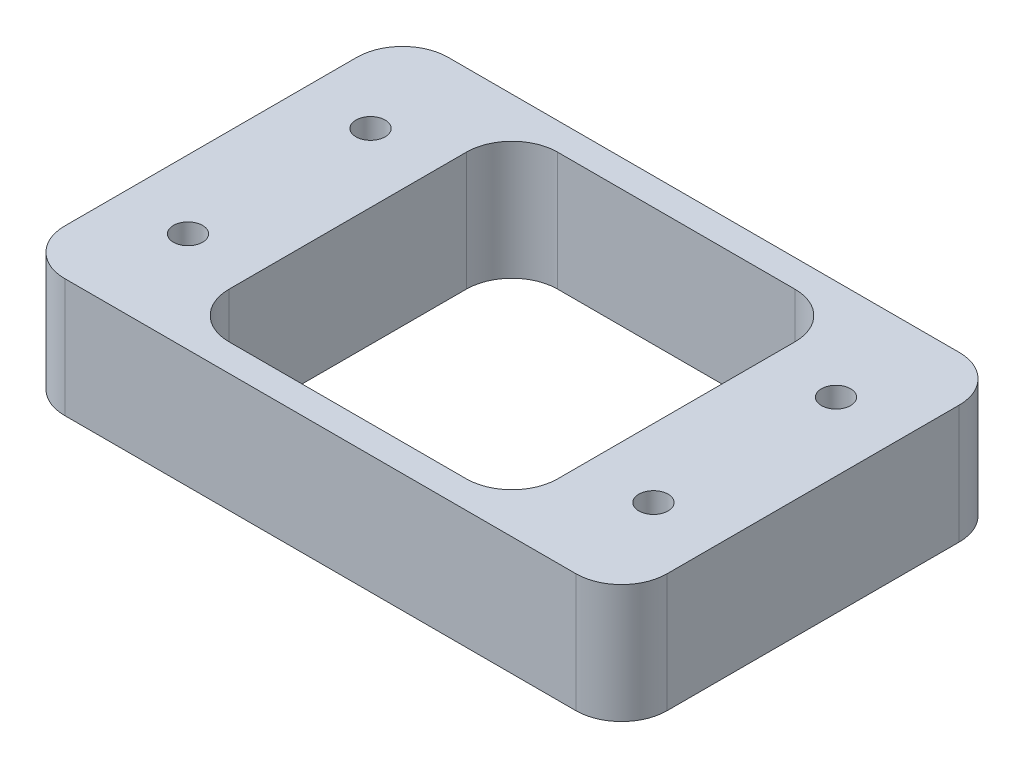
SolidWorks part; units mm, degrees
material "ABS"
ref_plane "Front Plane" through (0, 0, 0) normal (0, 0, 1) x (1, 0, 0)
ref_plane "Top Plane" through (0, 0, 0) normal (0, 1, 0) x (1, 0, 0)
ref_plane "Right Plane" through (0, 0, 0) normal (1, 0, 0) x (0, 0, -1)
sketch "Sketch1" plane through (0, 0, 0) normal (0, 1, 0) x (1, 0, 0)
  line L0 (7.5, 42) -> (7.5, 0) construction
  line L1 (0, 0) -> (66, 0)
  line L2 (0, 0) -> (0, 42)
  line L3 (0, 42) -> (66, 42)
  line L4 (66, 0) -> (66, 42)
  line L5 (33, 42) -> (33, 0) construction
  line L6 (66, 21) -> (0, 21) construction
  circle A0 centre (7.5, 31) radius 1.6
  circle A1 centre (7.5, 11) radius 1.6
  circle A2 centre (58.5, 11) radius 1.6
  circle A3 centre (58.5, 31) radius 1.6
  dimension "D3" = 20
  dimension "D4" = 3.2
  dimension "D1" = 66
  dimension "D2" = 42
  dimension "D5" = 7.5
extrude "Boss-Extrude1" add sketch "Sketch1" along normal blind 13
sketch "Sketch2" plane through (0, 13, 0) normal (0, 1, 0) x (1, 0, 0)
  line L0 (66, 42) -> (0, 42) construction
  line L5 (0, 21) -> (66, 21) construction
  line L6 (0, 42) -> (0, 0) construction
  line L7 (66, 0) -> (66, 42) construction
  line L8 (15, 3) -> (51, 3)
  line L9 (15, 3) -> (15, 39)
  line L10 (15, 39) -> (51, 39)
  line L11 (51, 3) -> (51, 39)
  line L12 (15, 3) -> (51, 39) construction
  line L13 (15, 39) -> (51, 3) construction
  point P0 (33, 21)
  dimension "D1" = 3
  dimension "D2" = 15
extrude "Cut-Extrude1" cut sketch "Sketch2" against normal through all
fillet "Fillet1" radius 5 8 edges at (0, 6.5, -42) (66, 6.5, -42) (66, 6.5, 0) (0, 6.5, 0) (51, 6.5, -3) (15, 6.5, -39) (51, 6.5, -39) (15, 6.5, -3)
